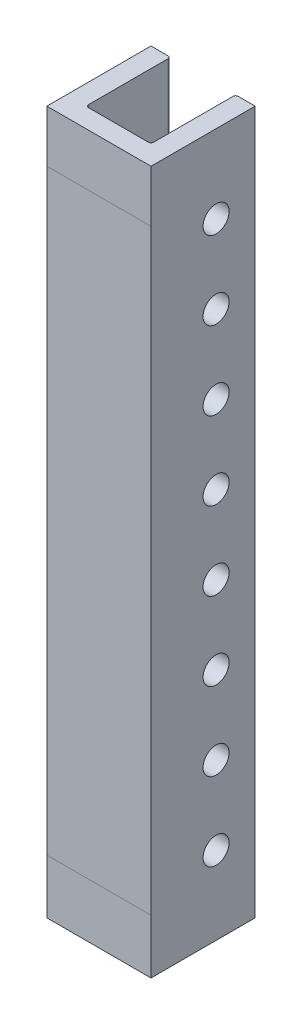
SolidWorks part; units mm, degrees
material "Plain Carbon Steel"
ref_plane "Front Plane" through (0, 0, 0) normal (0, 0, 1) x (1, 0, 0)
ref_plane "Top Plane" through (0, 0, 0) normal (0, 1, 0) x (1, 0, 0)
ref_plane "Right Plane" through (0, 0, 0) normal (1, 0, 0) x (0, 0, -1)
sketch "Sketch1" plane through (0, 0, 0) normal (0, 1, 0) x (1, 0, 0)
  line L0 (0, 0) -> (50.8, 0) construction
  line L1 (0, 0) -> (0, 9.525) construction
  line L2 (50.8, 0) -> (50.8, 9.525) construction
  line L3 (0, 9.525) -> (50.8, 9.525) construction
  line L4 (0, 0) -> (0, 50.8) construction
  line L5 (0, 50.8) -> (9.525, 50.8) construction
  line L6 (9.525, 50.8) -> (9.525, 9.525) construction
  line L7 (9.525, 9.525) -> (41.275, 9.525) construction
  line L8 (41.275, 9.525) -> (41.275, 50.8) construction
  line L9 (41.275, 50.8) -> (50.8, 50.8) construction
  line L10 (50.8, 50.8) -> (50.8, 9.525) construction
  line L11 (0, 0) -> (50.8, 0)
  line L12 (50.8, 0) -> (50.8, 50.8)
  line L13 (50.8, 50.8) -> (41.275, 50.8)
  line L14 (41.275, 50.8) -> (41.275, 9.525)
  line L15 (41.275, 9.525) -> (9.525, 9.525)
  line L16 (9.525, 9.525) -> (9.525, 50.8)
  line L17 (9.525, 50.8) -> (0, 50.8)
  line L18 (0, 50.8) -> (0, 0)
  point P0 (12.7, 9.525)
  dimension "D1" = 50.8
  dimension "D2" = 9.525
  dimension "D3" = 50.8
  dimension "D4" = 9.525
  dimension "D5" = 9.525
  dimension "D6" = 9.525
extrude "Boss-Extrude1" add sketch "Sketch1" along normal blind 342.9 contours L15 L16 L17 L18 L11 L12 L13 L14
sketch "Sketch2" plane through (50.8, 0, 0) normal (1, 0, 0) x (0, 0, -1)
  line L0 (31.75, 342.9) -> (31.75, 0) construction
  line L1 (0, 0) -> (50.8, 0) construction
  line L3 (31.75, 171.45) -> (0, 171.45) construction
  line L4 (0, 342.9) -> (0, 0) construction
  line L5 (0, 171.45) -> (50.8, 171.45) construction
  line L6 (50.8, 342.9) -> (50.8, 0) construction
  line L8 (0, 342.9) -> (50.8, 342.9) construction
  circle A0 centre (31.75, 304.8) radius 6.35
  circle A1 centre (31.75, 190.5) radius 6.35
  circle A2 centre (31.75, 228.6) radius 6.35
  circle A3 centre (31.75, 266.7) radius 6.35
  circle A4 centre (31.75, 76.2) radius 6.35
  circle A5 centre (31.75, 38.1) radius 6.35
  circle A7 centre (31.75, 152.4) radius 6.35
  circle A8 centre (31.75, 114.3) radius 6.35
  dimension "D1" = 38.1
  dimension "D2" = 171.45
  dimension "D5" = 12.7
  dimension "D6" = 12.7
  dimension "D7" = 12.7
  dimension "D8" = 152.4
  dimension "D11" = 12.7
  dimension "D12" = 12.7
  dimension "D13" = 12.7
  dimension "D15" = 12.7
  dimension "D16" = 12.7
  dimension "D3" = 76.2
  dimension "D4" = 114.3
  dimension "D9" = 19.05
  dimension "D10" = 190.5
  dimension "D14" = 228.6
  dimension "D17" = 38.1
  dimension "D18" = 38.1
  dimension "D19" = 38.1
extrude "Cut-Extrude1" cut sketch "Sketch2" against normal blind 304.8
fillet "Fillet1" radius 1.27 4 edges at (41.275, 171.45, -9.525) (9.525, 171.45, -50.8) (41.275, 171.45, -50.8) (9.525, 171.45, -9.525)
sketch "Sketch3" plane through (0, 0, 0) normal (0, 0, 1) x (1, 0, 0)
  line L0 (50.8, 342.9) -> (0, 342.9)
  line L1 (50.8, 342.9) -> (50.8, 317.5196)
  line L2 (0, 342.9) -> (0, 317.5196)
  line L3 (50.8, 317.5196) -> (0, 317.5196)
split line "Split Line1"
sketch "Sketch4" plane through (0, 0, 0) normal (0, 0, 1) x (1, 0, 0)
  line L0 (50.8, 0) -> (0, 0)
  line L1 (50.8, 0) -> (50.8, 26.5127)
  line L2 (0, 0) -> (0, 26.5127)
  line L3 (50.8, 26.5127) -> (0, 26.5127)
split line "Split Line3"
